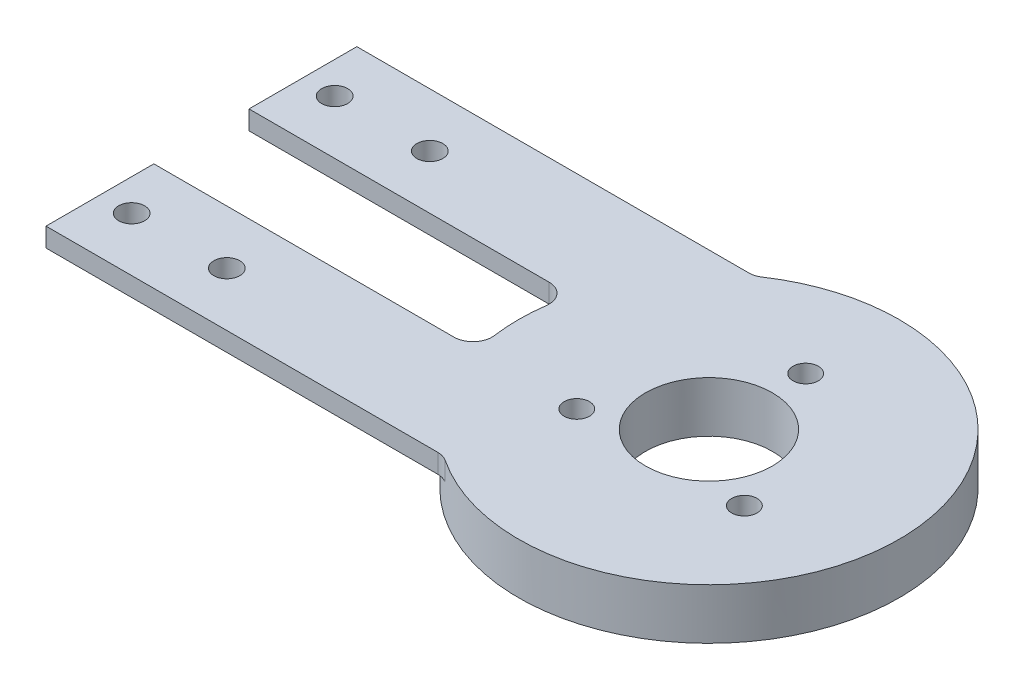
SolidWorks part; units mm, degrees
ref_plane "Front Plane" through (0, 0, 0) normal (0, 0, 1) x (1, 0, 0)
ref_plane "Top Plane" through (0, 0, 0) normal (0, 1, 0) x (1, 0, 0)
ref_plane "Right Plane" through (0, 0, 0) normal (1, 0, 0) x (0, 0, -1)
sketch "Sketch1" plane through (0, 0, 0) normal (0, 1, 0) x (1, 0, 0)
  circle A0 centre (0, 0) radius 30
  circle A1 centre (0, 0) radius 10
  circle A2 centre (0, 0) radius 15.25 construction
  circle A3 centre (0, 15.25) radius 2
  circle A4 centre (13.2069, -7.625) radius 2
  circle A5 centre (-13.2069, -7.625) radius 2
  point P8 (0, 0)
  point P9 (13.2069, -7.625)
  point P13 (0, 0)
  dimension "D1" = 30.5
  dimension "D2" = 60
  dimension "D3" = 20
  dimension "D4" = 4
  dimension "D5" = 3
extrude "Boss-Extrude1" add sketch "Sketch1" along normal blind 3
sketch "Sketch2" plane through (0, 3, 0) normal (0, 1, 0) x (1, 0, 0)
  line L1 (-80, 24.5) -> (-17, 24.5)
  line L2 (-80, 24.5) -> (-80, 7.5)
  line L3 (-80, 7.5) -> (-17, 7.5)
  line L4 (-17, 24.5) -> (-17, 7.5)
  line L5 (-80, -7.5) -> (-17, -7.5)
  line L6 (-80, -7.5) -> (-80, -24.5)
  line L7 (-80, -24.5) -> (-17, -24.5)
  line L8 (-17, -7.5) -> (-17, -24.5)
  circle A0 centre (0, 0) radius 10 construction
  dimension "D1" = 17
  dimension "D2" = 15
  dimension "D3" = 7.5
  dimension "D4" = 17
  dimension "D5" = 80
extrude "Boss-Extrude2" add sketch "Sketch2" against normal up to surface (3 mm away) up to face at (0, 0, 30)
sketch "Sketch3" plane through (0, 0, 0) normal (0, -1, 0) x (1, 0, 0)
  circle A0 centre (0, 0) radius 30
  arc A1 (-17.3133, -24.5) -> (-17.3133, 24.5) centre (0, 0) ccw construction
  circle A2 centre (0, -15.25) radius 2 construction
  circle A3 centre (13.2069, 7.625) radius 2 construction
  circle A4 centre (-13.2069, 7.625) radius 2 construction
  circle A5 centre (0, 0) radius 10 construction
  circle A6 centre (0, -15.25) radius 2
  circle A7 centre (13.2069, 7.625) radius 2
  circle A8 centre (-13.2069, 7.625) radius 2
  circle A9 centre (0, 0) radius 10
extrude "Boss-Extrude3" add sketch "Sketch3" along normal blind 5
sketch "Sketch4" plane through (0, 0, 0) normal (0, -1, 0) x (1, 0, 0)
  line L0 (-80, 24.5) -> (-80, 7.5) construction
  line L1 (-80, 7.5) -> (-29.0474, 7.5) construction
  line L2 (-80, -24.5) -> (-17.3133, -24.5) construction
  circle A0 centre (-75, 16) radius 2.05
  circle A1 centre (-60, 16) radius 2.05
  circle A2 centre (-75, -16) radius 2.05
  circle A3 centre (-60, -16) radius 2.05
  point P8 (0, 0)
  point P9 (0, 0)
  point P10 (0, 0)
  point P11 (0, 0)
  point P18 (0, 0)
  point P19 (0, 0)
  dimension "D1" = 4.1
  dimension "D2" = 5
  dimension "D3" = 15
  dimension "D4" = 8.5
  dimension "D5" = 8.5
extrude "Cut-Extrude1" cut sketch "Sketch4" against normal through all
fillet "Fillet1" radius 3 4 edges at (-17.3133, 1.5, -24.5) (-29.0474, 1.5, -7.5) (-29.0474, 1.5, 7.5) (-17.3133, 1.5, 24.5)
